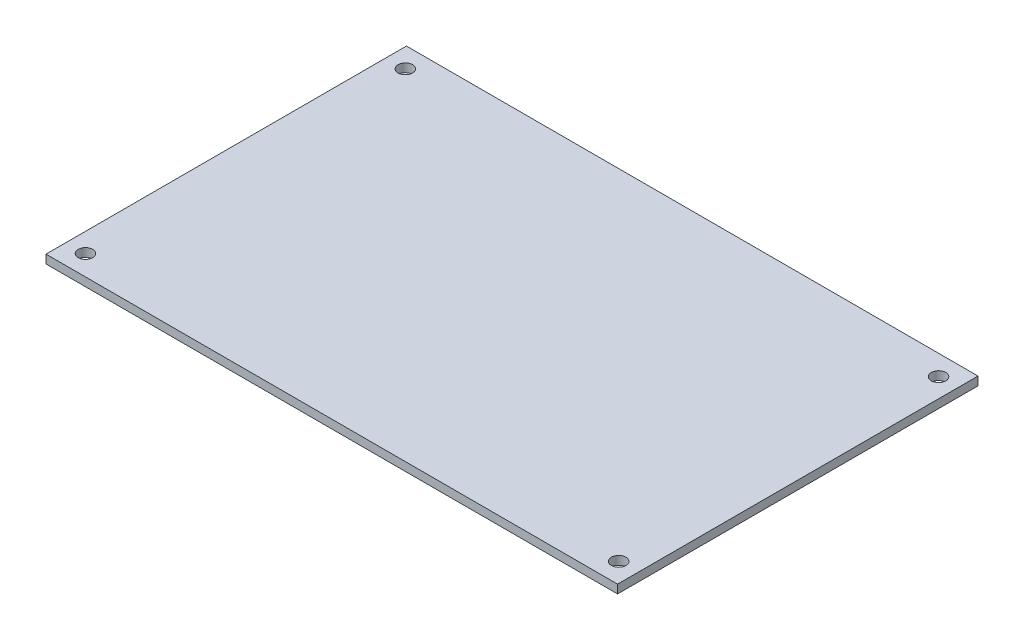
SolidWorks part; units mm, degrees
material "Thornel Mat VMA"
ref_plane "Front Plane" through (0, 0, 0) normal (0, 0, 1) x (1, 0, 0)
ref_plane "Top Plane" through (0, 0, 0) normal (0, 1, 0) x (1, 0, 0)
ref_plane "Right Plane" through (0, 0, 0) normal (1, 0, 0) x (0, 0, -1)
sketch "Sketch1" plane through (0, 0, 0) normal (0, 1, 0) x (1, 0, 0)
  line L1 (0, 0) -> (134, 0)
  line L2 (0, 0) -> (0, 84.5)
  line L3 (0, 84.5) -> (134, 84.5)
  line L4 (134, 0) -> (134, 84.5)
  dimension "D1" = 134
  dimension "D2" = 84.5
extrude "Boss-Extrude1" add sketch "Sketch1" along normal blind 2
sketch "Sketch2" plane through (0, 2, 0) normal (0, 1, 0) x (1, 0, 0)
  line L0 (67, 42.25) -> (67, 84.5) construction
  line L2 (134, 84.5) -> (0, 84.5) construction
  line L3 (129.5, 79.75) -> (4.5, 79.75) construction
  line L4 (129.5, 79.75) -> (129.5, 4.75) construction
  line L5 (129.5, 4.75) -> (4.5, 4.75) construction
  line L6 (4.5, 79.75) -> (4.5, 4.75) construction
  line L7 (129.5, 79.75) -> (4.5, 4.75) construction
  line L8 (129.5, 4.75) -> (4.5, 79.75) construction
  line L11 (0, 0) -> (134, 0) construction
  line L13 (134, 0) -> (134, 84.5) construction
  line L14 (67, 42.25) -> (134, 42.25) construction
  line L15 (67, 42.25) -> (0, 42.25) construction
  line L16 (0, 84.5) -> (0, 0) construction
  line L17 (67, 42.25) -> (67, 0) construction
  circle A0 centre (4.5, 4.75) radius 1.6
  circle A1 centre (4.5, 79.75) radius 1.6
  circle A2 centre (129.5, 79.75) radius 1.6
  circle A3 centre (129.5, 4.75) radius 1.6
  point P8 (67, 42.25)
  dimension "D1" = 3.2
  dimension "D2" = 125
  dimension "D3" = 75
hole_wizard "M3 Clearance Hole1" positions "Sketch4" profile "Sketch3" hole size "M3" standard "ANSI Metric"
sketch "Sketch4" plane through (0, 2, 0) normal (0, 1, 0) x (1, 0, 0)
  point P0 (4.5, 79.75)
  point P3 (129.5, 79.75)
  point P6 (129.5, 4.75)
  point P9 (4.5, 4.75)
sketch "Sketch3" plane through (4.5, 2, -79.75) normal (1, 0, 0) x (0, 0, 1)
  line L0 (0, 0) -> (0, 6.0215)
  line L1 (0, 6.0215) -> (1.7, 5)
  line L2 (1.7, 5) -> (1.7, 0)
  line L5 (1.7, 0) -> (0, 0)
  line L10 (0, 6.0215) -> (-1.7, 5) construction
  line L11 (0, -6.35) -> (0, 107.95) construction
  dimension "Hole Dia." = 3.4
  dimension "Hole Depth" = 5
  dimension "Drill Angle" = 118
